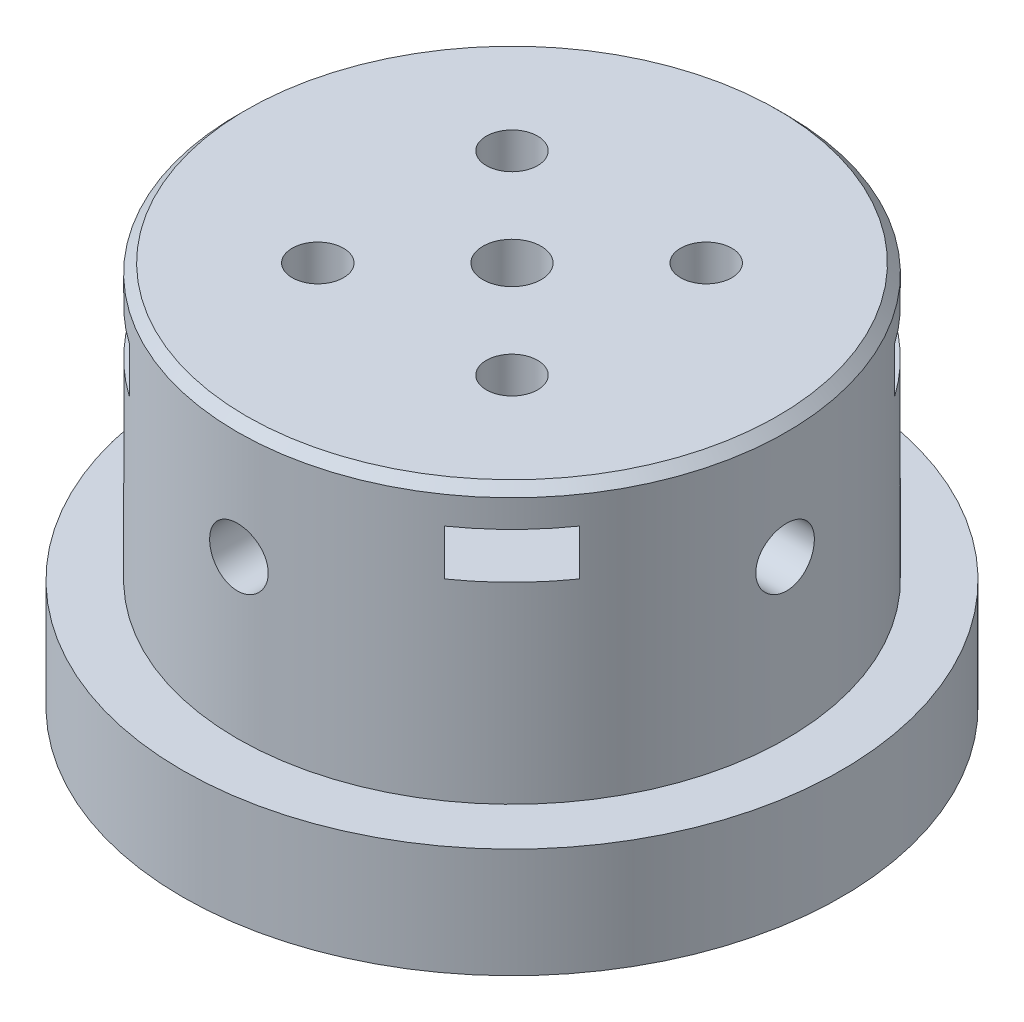
SolidWorks part; units mm, degrees
ref_plane "Front Plane" through (0, 0, 0) normal (0, 0, 1) x (1, 0, 0)
ref_plane "Top Plane" through (0, 0, 0) normal (0, 1, 0) x (1, 0, 0)
ref_plane "Right Plane" through (0, 0, 0) normal (1, 0, 0) x (0, 0, -1)
sketch "Sketch1" plane through (0, 0, 0) normal (0, 1, 0) x (1, 0, 0)
  circle A0 centre (0, 0) radius 15
  dimension "D1" = 30
extrude "Boss-Extrude1" add sketch "Sketch1" along normal blind 2
sketch "Sketch2" plane through (0, 2, 0) normal (0, 1, 0) x (1, 0, 0)
  circle A0 centre (0, 0) radius 13.5
  circle A1 centre (0, 0) radius 15
  circle A2 centre (0, 0) radius 15
  dimension "D1" = 0
  dimension "D2" = 1.5
extrude "Boss-Extrude2" add sketch "Sketch2" against normal up to surface (15 mm away)
sketch "Sketch3" plane through (0, -13, 0) normal (0, -1, 0) x (1, 0, 0)
  circle A0 centre (0, 0) radius 13.5 construction
  circle A1 centre (0, 0) radius 13.5
  circle A2 centre (0, 0) radius 18
  dimension "D1" = 36
extrude "Boss-Extrude3" add sketch "Sketch3" along normal up to surface (2 mm away)
sketch "Sketch4" plane through (0, -15, 0) normal (0, -1, 0) x (1, 0, 0)
  circle A0 centre (0, 0) radius 16.1
  circle A1 centre (0, 0) radius 18
  circle A2 centre (0, 0) radius 18
  dimension "D2" = 32.2
  dimension "D1" = 0
extrude "Boss-Extrude4" add sketch "Sketch4" along normal up to surface (3.9878 mm away)
chamfer "Chamfer1" distance 1 angle 45 1 edges at (0, -15, 13.5)
sketch "Sketch5" plane through (0, 2, 0) normal (0, 1, 0) x (1, 0, 0)
  circle A0 centre (0, 0) radius 13.5
  circle A1 centre (0, 0) radius 13.5 construction
extrude "Boss-Extrude5" add sketch "Sketch5" against normal up to surface (10.8216 mm away)
sketch "Sketch6" plane through (0, 2, 0) normal (0, 1, 0) x (1, 0, 0)
  circle A0 centre (0, 0) radius 1.5875
  dimension "D1" = 3.175
extrude "Cut-Extrude1" cut sketch "Sketch6" against normal through all both and the other way through all
sketch "Sketch7" plane through (0, 0, 0) normal (1, 0, 0) x (0, 0, -1)
  line L0 (0, 0) -> (0, -8.8216) construction
  line L1 (-1.5875, -8.8216) -> (1.5875, -8.8216) construction
  circle A0 centre (0, -4.4108) radius 1.6
  dimension "D1" = 3.2
extrude "Cut-Extrude2" cut sketch "Sketch7" against normal through all
ref_axis "Axis1" through (0, -14, 0) along (0, 1, 0)
ref_plane "Plane2" through (-10, 0, 0) normal (1, 0, 0) x (0, 0, -1)
ref_plane "Plane3" through (-9, 0, 0) normal (1, 0, 0) x (0, 0, -1)
sketch "Sketch11" plane through (-10, 0, 0) normal (1, 0, 0) x (0, 0, -1)
  circle A0 centre (0, -4.4108) radius 1.6 construction
  circle A1 centre (0, -4.4108) radius 1.6 construction
  circle A2 centre (0, -4.4108) radius 2
  dimension "D1" = 4
extrude "Cut-Extrude7" [suppressed] cut sketch "Sketch11" along normal blind 5.5
sketch "Sketch12" plane through (-10, 0, 0) normal (1, 0, 0) x (0, 0, -1)
  circle A0 centre (0, -4.4108) radius 3.5
  dimension "D1" = 7
extrude "Cut-Extrude8" [suppressed] cut sketch "Sketch12" against normal blind 5
chamfer "Chamfer2" [suppressed] distance 1 angle 45
pattern_circular "CirPattern3" count 4 over 360 about axis through (0, -14, 0) along (0, 1, 0) of "Cut-Extrude2", "Cut-Extrude7", "Cut-Extrude8", "Chamfer2"
sketch "Sketch13" plane through (-9, 0, 0) normal (1, 0, 0) x (0, 0, -1)
  line L0 (-2.75, -5.9985) -> (-2.75, -8.8216)
  line L1 (0, -7.5862) -> (2.75, -5.9985) construction
  line L2 (2.75, -5.9985) -> (2.75, -2.8231)
  line L3 (2.75, -2.8231) -> (0, -1.2354)
  line L4 (0, -1.2354) -> (-2.75, -2.8231)
  line L5 (-2.75, -2.8231) -> (-2.75, -5.9985)
  line L6 (-2.75, -5.9985) -> (0, -7.5862) construction
  line L7 (-2.75, -8.8216) -> (2.75, -8.8216)
  line L8 (2.75, -8.8216) -> (2.75, -5.9985)
  line L9 (-1.5875, -8.8216) -> (1.5875, -8.8216) construction
  circle A0 centre (0, -4.4108) radius 2.75 construction
  circle A1 centre (0, -4.4108) radius 1.6 construction
  dimension "D1" = 5.5
extrude "Cut-Extrude9" cut sketch "Sketch13" along normal blind 3
pattern_circular "CirPattern4" count 4 over 360 about axis through (0, -14, 0) along (0, 1, 0) of "Cut-Extrude9"
sketch "Sketch14" plane through (0, 2, 0) normal (0, -1, 0) x (1, 0, 0)
  line L0 (0, 0) -> (0, 13.5) construction
  line L1 (0, 0) -> (-9.5459, 9.5459) construction
  circle A0 centre (0, 0) radius 13.5 construction
  circle A1 centre (-5.3033, 5.3033) radius 1.4
  circle A2 centre (5.3033, 5.3033) radius 1.4
  circle A3 centre (5.3033, -5.3033) radius 1.4
  circle A4 centre (-5.3033, -5.3033) radius 1.4
  point P9 (0, 0)
  point P10 (0, 0)
  point P18 (0, 0)
  dimension "D3" = 2.8
  dimension "D1" = 45
  dimension "D2" = 7.5
  dimension "D4" = 4
extrude "Cut-Extrude10" cut sketch "Sketch14" along normal blind 4.5 and the other way through all
ref_plane "Plane4" through (0, 0, 0) normal (0, 1, 0) x (1, 0, 0)
sketch "Sketch15" plane through (0, 0, 0) normal (0, 1, 0) x (1, 0, 0)
  line L0 (0, 0) -> (-10.6066, 10.6066) construction
  line L1 (-8.2032, 4.5263) -> (-12.4451, 8.7681)
  line L2 (-7.4262, 7.4262) -> (-8.2032, 4.5263) construction
  line L3 (-8.2032, 4.5263) -> (-6.0803, 2.4034)
  line L4 (-6.0803, 2.4034) -> (-3.1804, 3.1804)
  line L5 (-3.1804, 3.1804) -> (-2.4034, 6.0803)
  line L6 (-2.4034, 6.0803) -> (-4.5263, 8.2032)
  line L7 (-4.5263, 8.2032) -> (-7.4262, 7.4262) construction
  line L8 (-12.4451, 8.7681) -> (-8.7681, 12.4451)
  line L9 (-8.7681, 12.4451) -> (-4.5263, 8.2032)
  line L10 (12.4451, 8.7681) -> (8.2032, 4.5263)
  line L11 (6.0803, 2.4034) -> (8.2032, 4.5263)
  line L12 (3.1804, 3.1804) -> (6.0803, 2.4034)
  line L13 (2.4034, 6.0803) -> (3.1804, 3.1804)
  line L14 (4.5263, 8.2032) -> (2.4034, 6.0803)
  line L15 (4.5263, 8.2032) -> (8.7681, 12.4451)
  line L16 (8.7681, 12.4451) -> (12.4451, 8.7681)
  line L17 (8.7681, -12.4451) -> (4.5263, -8.2032)
  line L18 (2.4034, -6.0803) -> (4.5263, -8.2032)
  line L19 (3.1804, -3.1804) -> (2.4034, -6.0803)
  line L20 (6.0803, -2.4034) -> (3.1804, -3.1804)
  line L21 (8.2032, -4.5263) -> (6.0803, -2.4034)
  line L22 (8.2032, -4.5263) -> (12.4451, -8.7681)
  line L23 (12.4451, -8.7681) -> (8.7681, -12.4451)
  line L24 (-12.4451, -8.7681) -> (-8.2032, -4.5263)
  line L25 (-6.0803, -2.4034) -> (-8.2032, -4.5263)
  line L26 (-3.1804, -3.1804) -> (-6.0803, -2.4034)
  line L27 (-2.4034, -6.0803) -> (-3.1804, -3.1804)
  line L28 (-4.5263, -8.2032) -> (-2.4034, -6.0803)
  line L29 (-4.5263, -8.2032) -> (-8.7681, -12.4451)
  line L30 (-8.7681, -12.4451) -> (-12.4451, -8.7681)
  circle A0 centre (0, 0) radius 15 construction
  circle A1 centre (-5.3033, 5.3033) radius 2.6 construction
  point P5 (-5.3033, 5.3033)
  point P8 (0, 0)
  point P18 (0, 0)
  point P41 (0, 0)
  dimension "D1" = 5.2
  dimension "D2" = 4
extrude "Cut-Extrude11" cut sketch "Sketch15" against normal blind 2.5
chamfer "Chamfer3" distance 0.5 angle 45 1 edges at (0, 2, 15)
